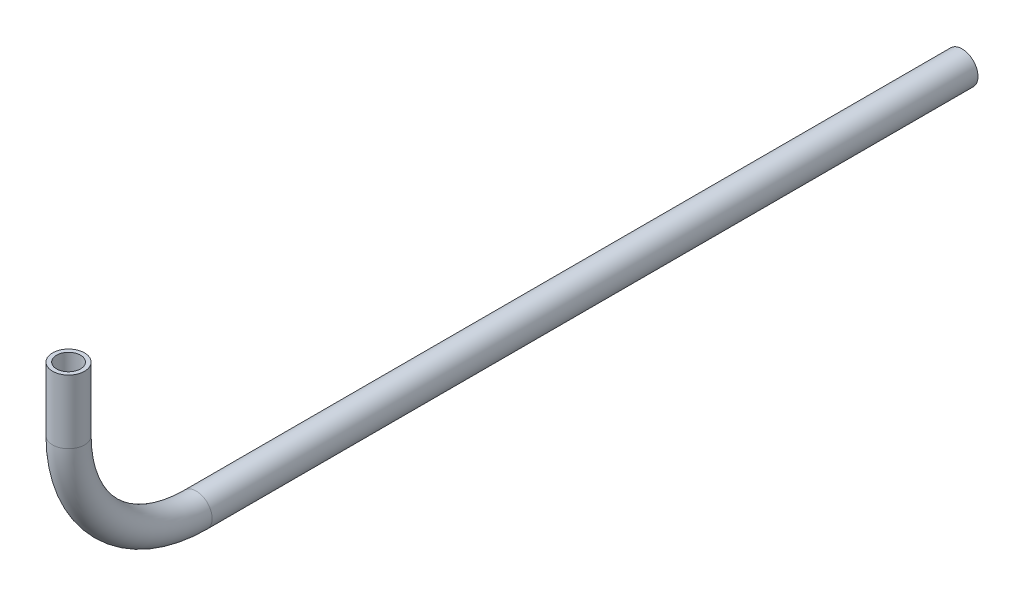
SolidWorks part; units mm, degrees
material "Silicon Rubber"
ref_plane "X-Y Datum" through (0, 0, 0) normal (0, 0, 1) x (1, 0, 0)
ref_plane "X-Z Datum" through (0, 0, 0) normal (0, 1, 0) x (1, 0, 0)
ref_plane "Y-Z Datum" through (0, 0, 0) normal (1, 0, 0) x (0, 0, -1)
sketch3d "3DSketch1"
  line L0 (0, 0, 0) -> (0, 0, 304.8)
  line L1 (0, 50.8, 355.6) -> (0, 76.2, 355.6)
  arc A0 (0, 0, 304.8) -> (0, 50.8, 355.6) centre (0, 50.8, 304.8) ccw
  point P4 (-50.8, 50.8, 304.8)
  dimension "D2" = 50.8
  dimension "D1" = 304.8
  dimension "D3" = 25.4
sweep "Sweep1" add path "3DSketch1" circular profile diameter 12.7 parameters "D3"=12.7
sweep "Cut-Sweep1" cut path "3DSketch1<3>" circular profile diameter 9.525 parameters "D3"=9.525
sketch3d "3DSketch1<3>" same geometry as "3DSketch1"
